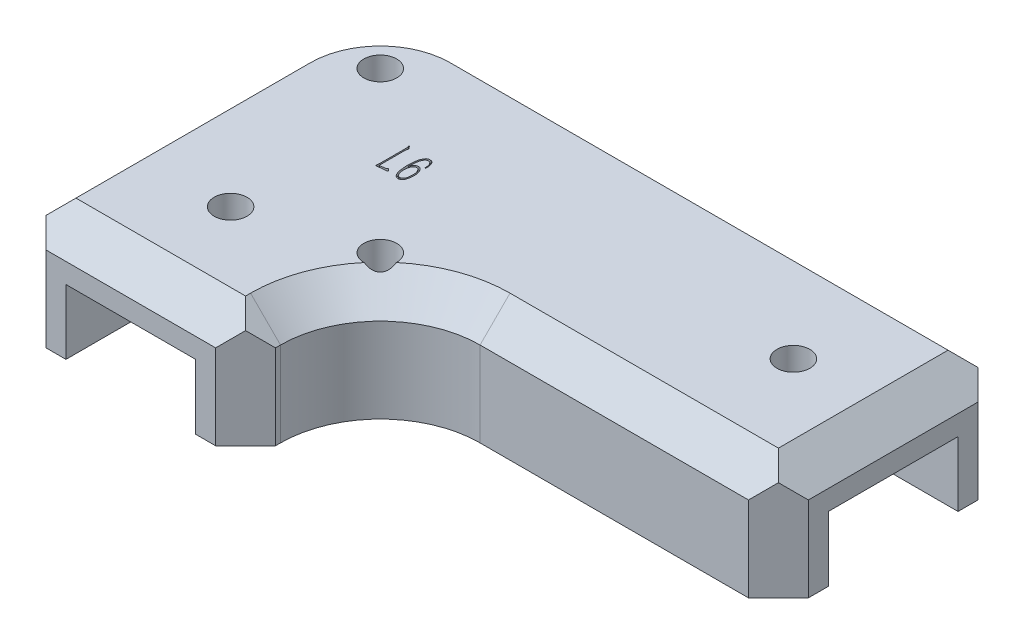
SolidWorks part; units mm, degrees
ref_plane "前视基准面" through (0, 0, 0) normal (0, 0, 1) x (1, 0, 0)
ref_plane "上视基准面" through (0, 0, 0) normal (0, 1, 0) x (1, 0, 0)
ref_plane "右视基准面" through (0, 0, 0) normal (1, 0, 0) x (0, 0, -1)
sketch "草图1" plane through (0, 0, 0) normal (0, 0, 1) x (1, 0, 0)
  line L1 (0, 0) -> (13, 0)
  line L2 (0, 0) -> (0, 13)
  line L3 (0, 13) -> (13, 13)
  line L4 (13, 0) -> (13, 13)
  line L5 (-5, 18) -> (18, 18)
  line L6 (-5, 18) -> (-5, -5)
  line L7 (-5, -5) -> (18, -5)
  line L8 (18, 18) -> (18, -5)
  dimension "D1" = 13
  dimension "D2" = 13
  dimension "D3" = 23
  dimension "D4" = 23
  dimension "D5" = 5
  dimension "D6" = 5
extrude "凸台-拉伸1" add sketch "草图1" along normal blind 36.5
sketch "草图2" plane through (0, -5, 0) normal (0, -1, 0) x (1, 0, 0)
  line L0 (-5, 36.5) -> (18, 36.5) construction
  line L1 (-5, 36.5) -> (-5, 0) construction
  circle A0 centre (6.5, 26.5) radius 1.65
  dimension "D1" = 3.3
  dimension "D2" = 10
  dimension "D3" = 11.5
extrude "切除-拉伸1" cut sketch "草图2" against normal blind 34
sketch "草图3" [suppressed] plane through (0, 25, 0) normal (0, 1, 0) x (1, 0, 0)
  line L0 (25, 0) -> (-5, 0) construction
  line L1 (2.5796, -2) -> (18.5796, -2)
  line L2 (2.5796, -2) -> (2.5796, -16)
  line L3 (2.5796, -16) -> (18.5796, -16)
  line L4 (18.5796, -2) -> (18.5796, -16)
  dimension "D1" = 14
  dimension "D2" = 2
  dimension "D3" = 16
sketch "草图4" plane through (18, 0, 0) normal (1, 0, 0) x (0, 0, -1)
  line L0 (-36.5, -5) -> (0, -5) construction
  line L1 (0, 18) -> (-23, 18)
  line L2 (0, 18) -> (0, -5)
  line L3 (0, -5) -> (-23, -5)
  line L4 (-23, 18) -> (-23, -5)
  circle A0 centre (-11.5, 6.5) radius 3
  dimension "D2" = 11.5
  dimension "D3" = 11.5
  dimension "D4" = 6
  dimension "D1" = 23
extrude "凸台-拉伸2" add sketch "草图4" along normal blind 29.9
sketch "草图5" plane through (47.9, 0, 0) normal (1, 0, 0) x (0, 0, -1)
  line L0 (0, -5) -> (0, 18) construction
  line L1 (-5, 0) -> (-18, 0)
  line L2 (-5, 0) -> (-5, 13)
  line L3 (-5, 13) -> (-18, 13)
  line L4 (-18, 0) -> (-18, 13)
  line L5 (-5, 0) -> (-18, 13) construction
  line L6 (-5, 13) -> (-18, 0) construction
  line L7 (-23, -5) -> (0, -5) construction
  point P0 (-11.5, 6.5)
  dimension "D1" = 13
  dimension "D2" = 13
  dimension "D3" = 5
  dimension "D4" = 5
extrude "拉伸-薄壁1" add sketch "草图5" along normal blind 10 thin thin type one direction wall 5
sketch "草图6" plane through (0, 18, 0) normal (0, 1, 0) x (1, 0, 0)
  line L0 (57.9, 0) -> (57.9, -23) construction
  line L1 (57.9, 0) -> (-5, 0) construction
  circle A0 centre (47.9, -11.5) radius 1.65
  dimension "D1" = 3.3
  dimension "D2" = 10
  dimension "D3" = 11.5
extrude "切除-拉伸2" cut sketch "草图6" against normal blind 39
sketch "草图7" plane through (47.9, 0, 0) normal (1, 0, 0) x (0, 0, -1)
  line L1 (-18, 13) -> (-5, 13)
  line L2 (-18, 13) -> (-18, 0)
  line L3 (-18, 0) -> (-5, 0)
  line L4 (-5, 13) -> (-5, 0)
extrude "切除-拉伸3" cut sketch "草图7" against normal blind 39.4
chamfer "倒角1" distance 3 angle 45 1 edges at (13, 6.5, 18)
chamfer "倒角2" [suppressed] distance 3 angle 45
sketch "草图8" plane through (0, -5, 0) normal (0, -1, 0) x (1, 0, 0)
  line L1 (-5, 36.5) -> (57.9, 36.5)
  line L2 (-5, 36.5) -> (-5, 0)
  line L3 (-5, 0) -> (57.9, 0)
  line L4 (57.9, 36.5) -> (57.9, 0)
extrude "切除-拉伸4" cut sketch "草图8" against normal blind 11.5
sketch "草图9" plane through (0, 13, 0) normal (0, -1, 0) x (1, 0, 0)
  line L0 (13, 5) -> (0, 18)
  line L2 (0, 18) -> (0, 0)
  line L3 (0, 0) -> (13, 0)
  line L4 (13, 0) -> (13, 5)
  dimension "D1" = 18
extrude "凸台-拉伸3" add sketch "草图9" along normal blind 6.5
fillet "圆角1" radius 10 1 edges at (-5, 12.25, 0)
fillet "圆角2" radius 10 1 edges at (18, 12.25, 23)
sketch "草图10" plane through (0, 6.5, 0) normal (0, -1, 0) x (1, 0, 0)
  line L0 (-5, 36.5) -> (-5, 10) construction
  line L1 (5, 0) -> (57.9, 0) construction
  line L2 (57.9, 18) -> (16, 18) construction
  line L3 (13, 21) -> (13, 36.5) construction
  circle A0 centre (2, 7) radius 1.65
  circle A1 centre (18, 23) radius 1.65
  dimension "D1" = 7
  dimension "D2" = 7
  dimension "D3" = 3.3
  dimension "D4" = 5
  dimension "D5" = 5
  dimension "D6" = 3.3
extrude "切除-拉伸5" cut sketch "草图10" against normal blind 28.5
chamfer "倒角3" distance 3 angle 45 6 edges at (18, 18, 34.75) (42.95, 18, 23) (20.9289, 18, 25.9289) (31.45, 18, 0) (-2.0711, 18, 2.9289) (-5, 18, 23.25)
chamfer "倒角4" distance 3 angle 45 2 edges at (57.9, 18, 11.5) (6.5, 18, 36.5)
chamfer "倒角5" distance 3 angle 45 4 edges at (57.9, 10.75, 0) (57.9, 10.75, 23) (18, 10.75, 36.5) (-5, 10.75, 36.5)
sketch "草图11" plane through (0, 18, 0) normal (0, 1, 0) x (1, 0, 0)
  text T0 "L6"
extrude "切除-拉伸6" cut sketch "草图11" against normal blind 0.3
